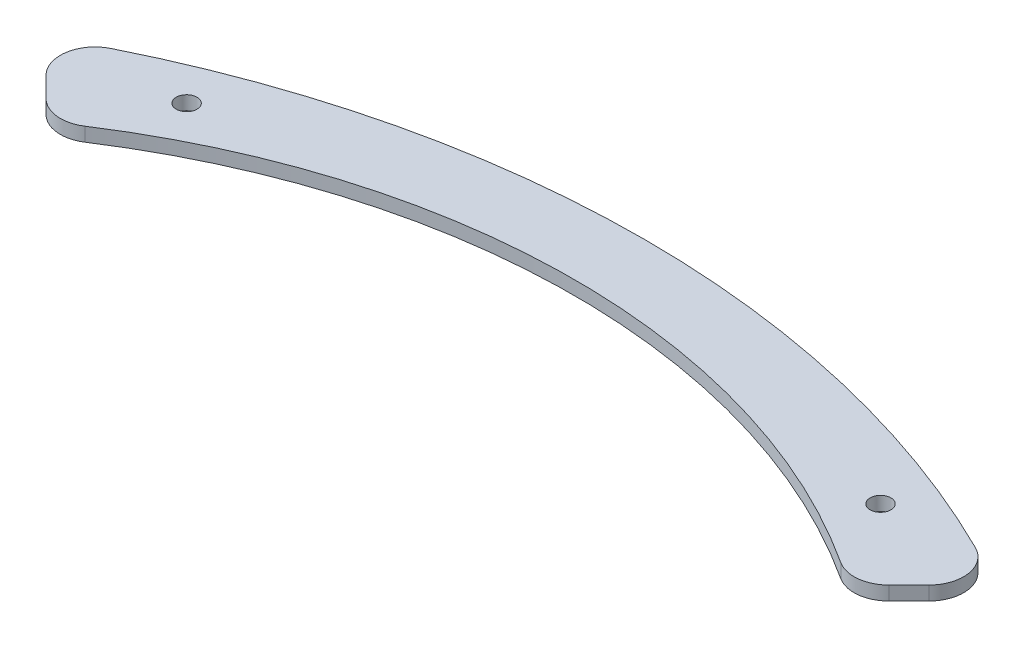
SolidWorks part; units mm, degrees
material "1060 Alloy"
ref_plane "Front Plane" through (0, 0, 0) normal (0, 0, 1) x (1, 0, 0)
ref_plane "Top Plane" through (0, 0, 0) normal (0, 1, 0) x (1, 0, 0)
ref_plane "Right Plane" through (0, 0, 0) normal (1, 0, 0) x (0, 0, -1)
sketch "Sketch1" plane through (0, 0, 0) normal (0, 1, 0) x (1, 0, 0)
  line L0 (-68.4085, 122.1486) -> (-57.8019, 111.542)
  line L1 (68.4085, 122.1486) -> (57.8019, 111.542)
  line L3 (0, 0) -> (-117.9329, 117.9329) construction
  line L4 (0, 0) -> (118.2874, 118.2874) construction
  line L5 (0, 0) -> (0, 174.1104) construction
  line L6 (-15, 129.1317) -> (15, 129.1317) construction
  line L7 (-15, 129.1317) -> (-15, 118.1317) construction
  line L8 (-15, 118.1317) -> (15, 118.1317) construction
  line L9 (15, 129.1317) -> (15, 118.1317) construction
  arc A0 (-68.4085, 122.1486) -> (68.4085, 122.1486) centre (0, 0) cw
  arc A1 (-57.8019, 111.542) -> (57.8019, 111.542) centre (0, 29.9396) cw
  circle A2 centre (0, 0) radius 130 construction
  dimension "D1" = 140
  dimension "D6" = 100
  dimension "D7" = 10
  dimension "D2" = 15
  dimension "D3" = 45
  dimension "D4" = 38
  dimension "D5" = 38
  dimension "D8" = 11
  dimension "D9" = 30
extrude "Boss-Extrude1" add sketch "Sketch1" along normal blind 2
fillet "Fillet1" radius 5 4 edges at (68.4085, 1, -122.1486) (57.8019, 1, -111.542) (-68.4085, 1, -122.1486) (-57.8019, 1, -111.542)
sketch "Sketch2" plane through (0, 2, 0) normal (0, 1, 0) x (1, 0, 0)
  circle A0 centre (-50, 124) radius 1.5
  circle A1 centre (50, 124) radius 1.5
  dimension "D1" = 3
  dimension "D2" = 124
  dimension "D3" = 50
  dimension "D4" = 50
extrude "Cut-Extrude1" cut sketch "Sketch2" against normal up to next
